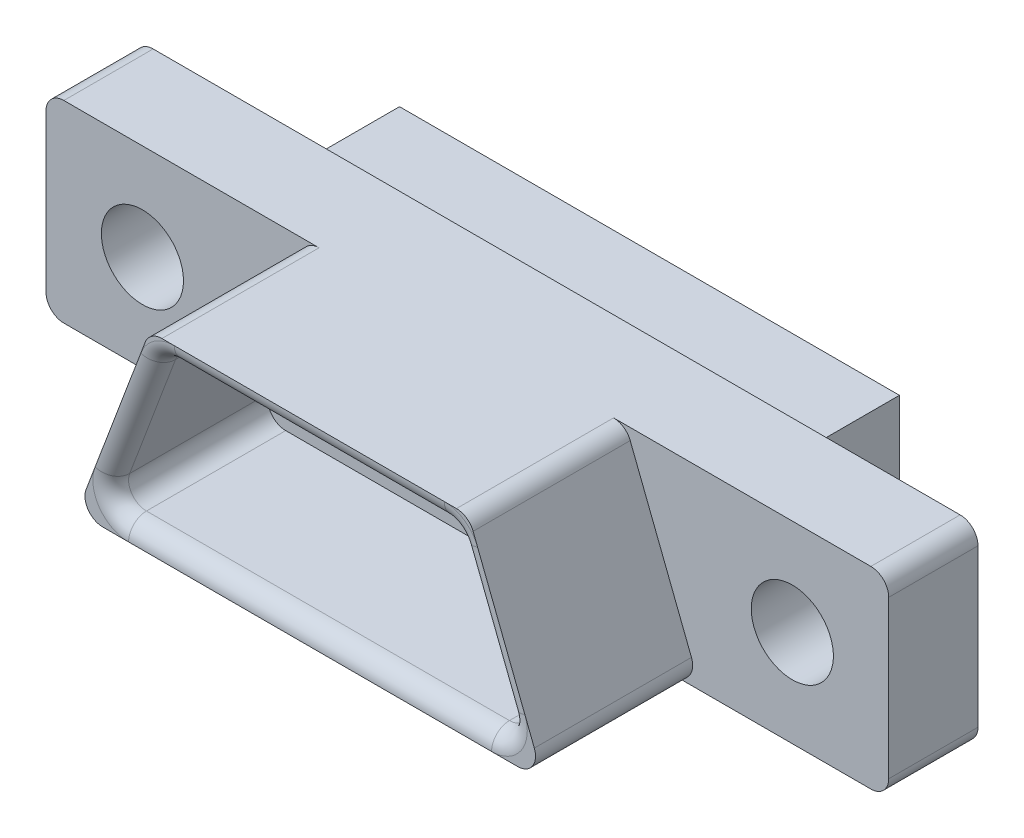
SolidWorks part; units mm, degrees
ref_plane "前视基准面" through (0, 0, 0) normal (0, 0, 1) x (1, 0, 0)
ref_plane "上视基准面" through (0, 0, 0) normal (0, 1, 0) x (1, 0, 0)
ref_plane "右视基准面" through (0, 0, 0) normal (1, 0, 0) x (0, 0, -1)
sketch "草图1" plane through (0, 0, 0) normal (0, 0, 1) x (1, 0, 0)
  line L0 (0, -5.928) -> (0, 7.248) construction
  line L1 (-11.8, -2.7) -> (11.8, -2.7)
  line L2 (-11.8, -2.7) -> (-11.8, 2.7)
  line L3 (-11.8, 2.7) -> (11.8, 2.7)
  line L4 (11.8, -2.7) -> (11.8, 2.7)
  line L5 (-12.0076, 0) -> (16.0041, 0) construction
  circle A0 centre (-9.1, 0) radius 1.15
  circle A1 centre (9.1, 0) radius 1.15
  dimension "D1" = 9.1
extrude "凸台-拉伸1" add sketch "草图1" along normal blind 2.5
fillet "圆角1" radius 0.5 1 edges at (-11.8, 2.7, 1.25)
fillet "圆角2" radius 0.5 3 edges at (-11.8, -2.7, 1.25) (11.8, -2.7, 1.25) (11.8, 2.7, 1.25)
sketch "草图3" plane through (0, 0, 0) normal (0, 0, -1) x (-1, 0, 0)
  line L1 (-7, 2.15) -> (7, 2.15)
  line L2 (-7, 2.15) -> (-7, -2.15)
  line L3 (-7, -2.15) -> (7, -2.15)
  line L4 (7, 2.15) -> (7, -2.15)
  dimension "D1" = 14
  dimension "D2" = 4.3
  dimension "D3" = 7
  dimension "D4" = 2.15
extrude "凸台-拉伸2" add sketch "草图3" along normal blind 2.6
sketch "草图4" plane through (0, 0, -2.6) normal (0, 0, -1) x (-1, 0, 0)
  line L0 (0, 3.2827) -> (0, -3.6632) construction
  circle A1 centre (0, 0.55) radius 0.31
  circle A2 centre (1.27, 0.55) radius 0.31
  circle A3 centre (2.54, 0.55) radius 0.31
  circle A4 centre (3.81, 0.55) radius 0.31
  circle A5 centre (-3.81, 0.55) radius 0.31
  circle A6 centre (-2.54, 0.55) radius 0.31
  circle A7 centre (-1.27, 0.55) radius 0.31
  circle A8 centre (-4.445, -0.55) radius 0.31
  circle A9 centre (-3.175, -0.55) radius 0.31
  circle A10 centre (-1.905, -0.55) radius 0.31
  circle A11 centre (-0.635, -0.55) radius 0.31
  circle A12 centre (0.635, -0.55) radius 0.31
  circle A13 centre (1.905, -0.55) radius 0.31
  circle A14 centre (3.175, -0.55) radius 0.31
  circle A15 centre (4.445, -0.55) radius 0.31
  dimension "D1" = 4
  dimension "D2" = 8
extrude "切除-拉伸1" cut sketch "草图4" against normal blind 4.5
sketch "草图5" plane through (0, 0, 2.5) normal (0, 0, 1) x (1, 0, 0)
  line L0 (-4.1539, 2.7) -> (4.0946, 2.7)
  line L1 (-5.8095, -2.7) -> (5.8095, -2.7)
  line L2 (-4.6219, 2.3761) -> (-6.2775, -2.0239)
  line L3 (4.5605, 2.3816) -> (6.2754, -2.0184)
  line L4 (-3.8078, 2.2) -> (3.7528, 2.2)
  line L5 (4.2187, 1.8816) -> (5.5439, -1.5184)
  line L6 (-5.0871, -2.2) -> (5.078, -2.2)
  line L7 (-4.2758, 1.8761) -> (-5.5551, -1.5239)
  line L8 (-4.1539, 2.2) -> (4.0946, 2.2) construction
  line L9 (4.0946, 2.2) -> (5.8095, -2.2) construction
  line L10 (-5.8095, -2.2) -> (5.8095, -2.2) construction
  line L11 (-4.1539, 2.2) -> (-5.8095, -2.2) construction
  line L12 (4.4857, 2.5735) -> (6.3461, -2.1998) construction
  line L13 (-4.2923, 2.7) -> (4.3083, 2.7) construction
  line L14 (-5.8104, -2.7) -> (6.0985, -2.7) construction
  line L15 (-4.5731, 2.5057) -> (-6.3792, -2.2943) construction
  arc A0 (4.2187, 1.8816) -> (3.7528, 2.2) centre (3.7528, 1.7) ccw
  arc A1 (5.078, -2.2) -> (5.5439, -1.5184) centre (5.078, -1.7) ccw
  arc A9 (-5.0871, -2.2) -> (-5.5551, -1.5239) centre (-5.0871, -1.7) cw
  arc A11 (4.0946, 2.2) -> (4.0946, 2.2) centre (4.0946, 2.2) cw construction
  arc A12 (5.8095, -2.2) -> (5.8095, -2.2) centre (5.8095, -2.2) ccw construction
  arc A13 (-5.8095, -2.2) -> (-5.8095, -2.2) centre (-5.8095, -2.2) cw construction
  arc A14 (-4.1539, 2.2) -> (-4.1539, 2.2) centre (-4.1539, 2.2) ccw construction
  arc A15 (-4.2758, 1.8761) -> (-3.8078, 2.2) centre (-3.8078, 1.7) cw
  arc A16 (-5.8104, -2.7) -> (-6.3792, -2.2943) centre (-6.0948, -2.4972) cw construction
  arc A17 (-4.2923, 2.7) -> (-4.5731, 2.5057) centre (-4.2923, 2.4) ccw construction
  arc A18 (6.0985, -2.7) -> (6.3461, -2.1998) centre (6.1236, -2.4011) ccw construction
  arc A19 (4.3083, 2.7) -> (4.4857, 2.5735) centre (4.2346, 2.4092) cw construction
  arc A20 (4.5605, 2.3816) -> (4.0946, 2.7) centre (4.0946, 2.2) ccw
  arc A21 (6.2754, -2.0184) -> (5.8095, -2.7) centre (5.8095, -2.2) cw
  arc A22 (-4.6219, 2.3761) -> (-4.1539, 2.7) centre (-4.1539, 2.2) cw
  arc A23 (-5.8095, -2.7) -> (-6.2775, -2.0239) centre (-5.8095, -2.2) cw
  point P4 (0, -2.7)
  dimension "D6" = 0.5
  dimension "D1" = 0.5
  dimension "D3" = 0
  dimension "D5" = 0.5
extrude "凸台-拉伸3" add sketch "草图5" along normal blind 4.4
fillet "圆角3" radius 0.5 8 edges at (-4.0924, 2.1111, 6.9) (-0.0275, 2.2, 6.9) (4.035, 2.1128, 6.9) (4.8813, 0.1816, 6.9) (5.4908, -1.9821, 6.9) (-0.0046, -2.2, 6.9) (-5.4983, -1.9846, 6.9) (-4.9155, 0.1761, 6.9)
equation "\"23..6mm\"=11.36"
